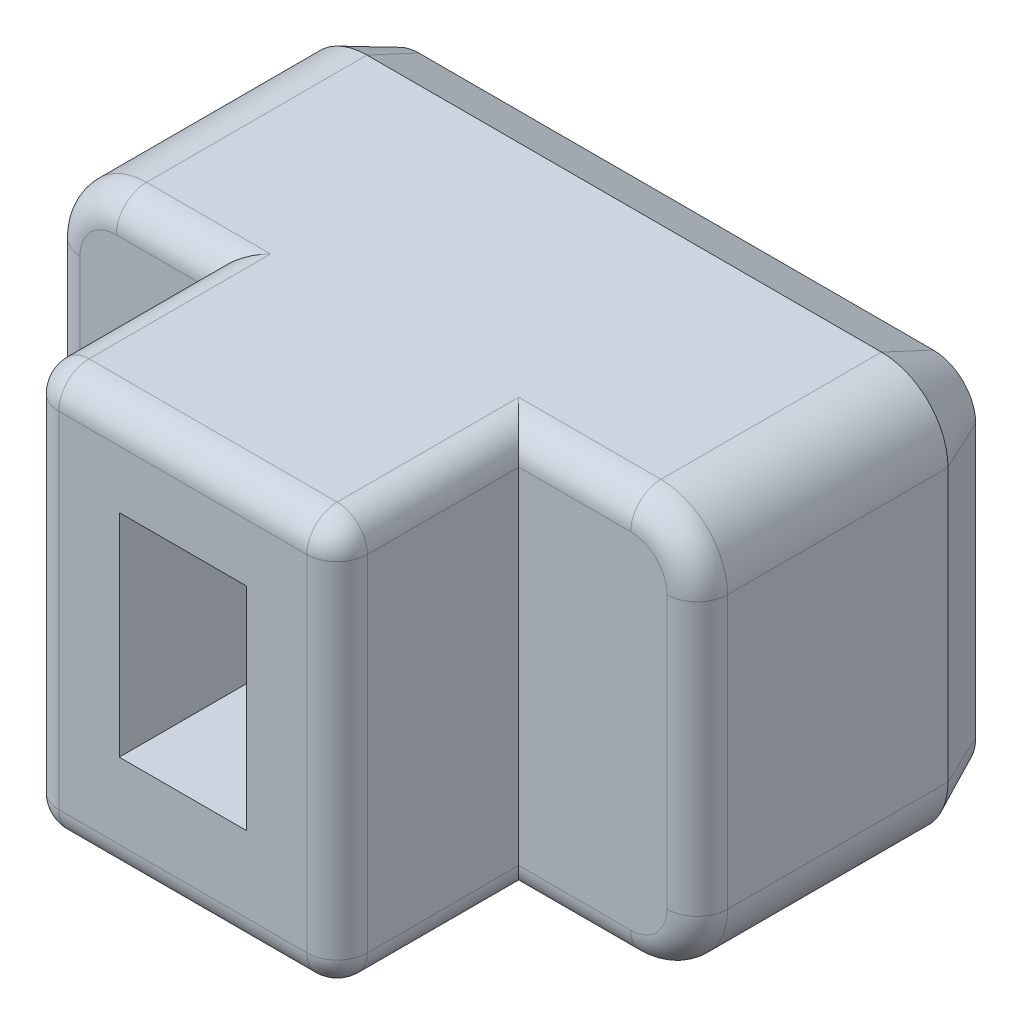
SolidWorks part; units mm, degrees
ref_plane "Plan de face" through (0, 0, 0) normal (0, 0, 1) x (1, 0, 0)
ref_plane "Plan de dessus" through (0, 0, 0) normal (0, 1, 0) x (1, 0, 0)
ref_plane "Plan de droite" through (0, 0, 0) normal (1, 0, 0) x (0, 0, -1)
sketch "Esquisse2" plane through (0, 0, 0) normal (0, 0, 1) x (1, 0, 0)
  line L1 (1.1, 0) -> (9.6, 0)
  line L2 (0, 1.1) -> (0, 5.6)
  line L3 (1.1, 6.7) -> (9.6, 6.7)
  line L4 (10.7, 1.1) -> (10.7, 5.6)
  arc A0 (9.6, 6.7) -> (10.7, 5.6) centre (9.6, 5.6) cw
  arc A1 (9.6, 0) -> (10.7, 1.1) centre (9.6, 1.1) ccw
  arc A2 (1.1, 0) -> (0, 1.1) centre (1.1, 1.1) cw
  arc A3 (0, 5.6) -> (1.1, 6.7) centre (1.1, 5.6) cw
  point P7 (10.7, 6.7)
  point P12 (0, 0)
  point P15 (0, 6.7)
  dimension "D3" = 1.1
  dimension "D1" = 10.7
  dimension "D2" = 6.7
extrude "Boss.-Extru.1" add sketch "Esquisse2" along normal blind 8
sketch "Esquisse3" plane through (0, 0, 8) normal (0, 0, 1) x (1, 0, 0)
  line L0 (0, 5.6) -> (0, 1.1) construction
  line L1 (4.15, 5.25) -> (6.25, 5.25)
  line L2 (4.15, 5.25) -> (4.15, 1.75)
  line L3 (4.15, 1.75) -> (6.25, 1.75)
  line L4 (6.25, 5.25) -> (6.25, 1.75)
  line L5 (10.7, 1.1) -> (10.7, 5.6) construction
  line L6 (9.6, 6.7) -> (1.1, 6.7) construction
  line L7 (1.1, 0) -> (9.6, 0) construction
  dimension "D1" = 2.1
  dimension "D2" = 3.5
  dimension "D3" = 4.15
  dimension "D4" = 4.45
  dimension "D5" = 1.45
  dimension "D6" = 1.75
extrude "Enlèv. mat.-Extru.1" cut sketch "Esquisse3" against normal blind 3
sketch "Esquisse4" plane through (0, 0, 8) normal (0, 0, 1) x (1, 0, 0)
  line L0 (2.65, 6.7) -> (2.65, 0)
  line L1 (9.6, 6.7) -> (1.1, 6.7) construction
  line L2 (1.1, 0) -> (9.6, 0) construction
  line L3 (2.65, 0) -> (7.75, 0)
  line L4 (7.75, 0) -> (7.75, 6.7)
  line L5 (7.75, 6.7) -> (2.65, 6.7)
  line L6 (4.15, 5.25) -> (4.15, 1.75) construction
  line L7 (6.25, 1.75) -> (6.25, 5.25) construction
  dimension "D1" = 1.5
  dimension "D2" = 1.5
extrude "Enlèv. mat.-Extru.2" cut sketch "Esquisse4" against normal blind 3 flip side to cut
fillet "Congé1" radius 0.5 18 edges at (8.675, 0, 5) (10.3778, 0.3222, 5) (10.7, 3.35, 5) (10.3778, 6.3778, 5) (1.875, 6.7, 5) (0.3222, 6.3778, 5) (1.875, 0, 5) (0.3222, 0.3222, 5) (7.75, 6.7, 6.5) (2.65, 6.7, 6.5) (7.75, 0, 6.5) (2.65, 0, 6.5) (2.65, 3.35, 8) (5.2, 6.7, 8) (7.75, 3.35, 8) (5.2, 0, 8) (8.675, 6.7, 5) (0, 3.35, 5)
chamfer "Chanfrein1" distance 0.4 angle 65 8 edges at (5.35, 0, 0) (10.3778, 0.3222, 0) (0.3222, 0.3222, 0) (10.7, 3.35, 0) (0, 3.35, 0) (10.3778, 6.3778, 0) (0.3222, 6.3778, 0) (5.35, 6.7, 0) first distance on face at (5.35, 3.35, 0)
sketch "Esquisse5" plane through (0, 0, 0) normal (0, 0, 1) x (1, 0, 0)
  line L0 (-0.9378, 5.093) -> (11.6517, 5.093) construction
  text T0 "PROC" font "Corbel" height 3.5
extrude "Enlèv. mat.-Extru.3" cut sketch "Esquisse5" along normal blind 0.2
extrude "Boss.-Extru.2" add sketch "Esquisse5<4>" against normal blind 0.2
sketch "Esquisse5<4>" plane through (0, 0, 0) normal (0, 0, 1) x (1, 0, 0) same geometry as "Esquisse5"
